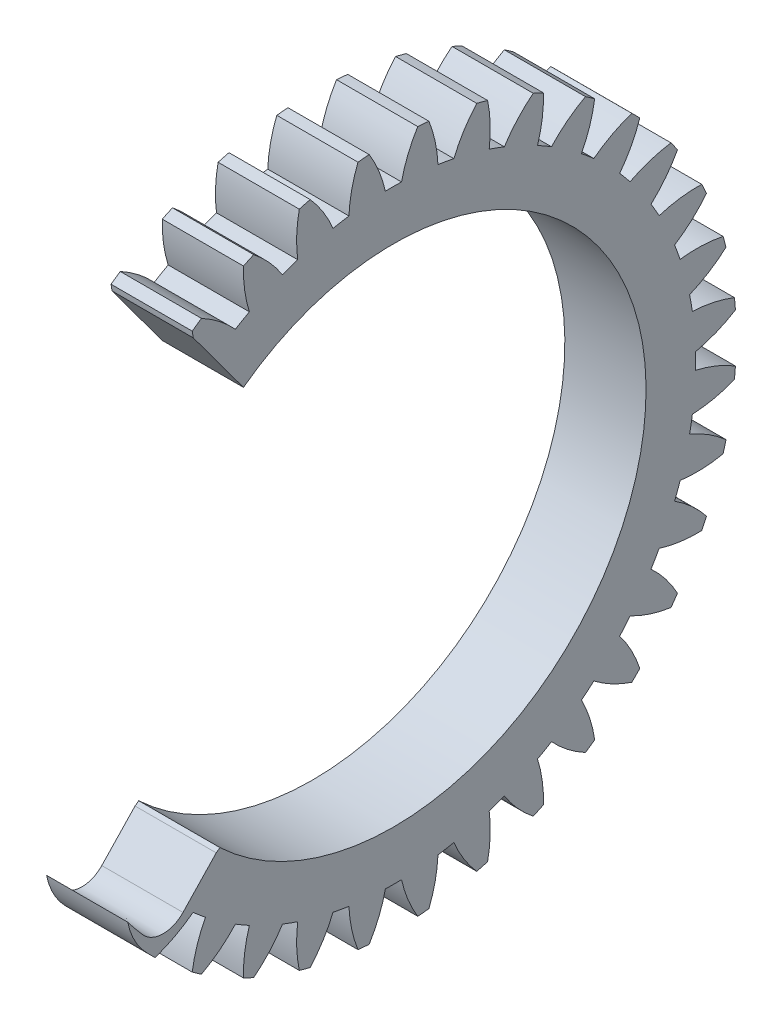
SolidWorks part; units mm, degrees
ref_plane "Plane1" through (0, 0, 0) normal (0, 0, 1) x (1, 0, 0)
ref_plane "Plane2" through (0, 0, 0) normal (0, 1, 0) x (1, 0, 0)
ref_plane "Plane3" through (0, 0, 0) normal (1, 0, 0) x (0, 0, -1)
sketch "HoldingSke" plane through (0, 0, 0) normal (0, 1, 0) x (1, 0, 0)
  line L0 (0, 0) -> (0.4045, -0.2939)
  line L1 (-15, 0) -> (100, 0) construction
  line L2 (0, 0) -> (-2.1039, 2.3779)
  line L3 (0, 0) -> (-11.863, 4.5341)
  line L4 (0, 0) -> (6.9867, 5.0761)
  line L5 (0, 0) -> (-46.8476, -17.4728)
  line L6 (0, 0) -> (-7.4607, -5.0337)
  line L7 (-2.1039, 2.3779) -> (8.6586, 51.2059)
  line L8 (-76.2, 54.61) -> (-71.9, 54.61)
  line L9 (-71.009, 38.7566) -> (-53.1078, 45.2721)
  line L10 (-76.2, 71.12) -> (104.1128, 71.12)
  line L11 (0, 0) -> (-9, 0)
  line L12 (-76.2, 101.6) -> (-76.133, 101.6)
  line L13 (24.9733, 27.94) -> (52.9518, 28.4284)
  line L14 (24.9733, 27.94) -> (24.9743, 27.94)
  line L15 (24.9733, 27.94) -> (100.4006, 29.5858)
  line L16 (-63.627, -2) -> (-12.827, -2)
  circle A0 centre (0, 0) radius 28
  circle A1 centre (0, 0) radius 33.499
  circle A2 centre (0, 0) radius 37.5
  circle A3 centre (0, 0) radius 28
  dimension "Num_teeth" = 36
  dimension "Pitch_radius" = 180.3128
  dimension "Width" = 9
  dimension "Thickness" = 9
sketch "BasProSke" plane through (0, 0, 0) normal (0, 1, 0) x (1, 0, 0)
  line L0 (-10, 0) -> (60, 0) construction
  line L1 (0, 0) -> (0, 38)
  line L2 (0, 0) -> (9, 0)
  line L3 (9, 0) -> (9, 38)
  line L4 (9, 38) -> (0, 38)
  dimension "Thickness" = 9
  dimension "Diameter" = 76
revolve "Base-Revolve" add sketch "BasProSke" angle 360 about L0
sketch "TooCutSke" plane through (0, 0, 0) normal (1, 0, 0) x (0, 0, -1)
  line L1 (0, 0) -> (0, 107) construction
  line L2 (0, 0) -> (-1.6875, 35.9604) construction
  line L3 (0, 0) -> (-6.2701, 71.6676) construction
  line L4 (-1.6875, 35.9604) -> (-3.135, 35.8338) construction
  arc A0 (0.8949, 33.487) -> (-0.8949, 33.487) centre (0, 0) ccw
  arc A1 (2.7061, 37.929) -> (-2.7061, 37.929) centre (0, 0) ccw
  circle A2 centre (0, 0) radius 36 construction
  circle A3 centre (0, 0) radius 33.8289 construction
  arc A4 (-0.8949, 33.487) -> (-2.7061, 37.929) centre (-14.9484, 30.347) ccw
  arc A5 (2.7061, 37.929) -> (0.8949, 33.487) centre (14.9484, 30.347) ccw
extrude "ToothCut" cut sketch "TooCutSke" along normal through all
fillet "Breaks" [suppressed] radius 0.04 tangent propagation no
fillet "RootFillets" [suppressed] radius 0.501
pattern_circular "TeethCuts" count 36 every 10 about axis through (-10, 0, 0) along (1, 0, 0) of "ToothCut", "RootFillets", "Breaks"
sketch "HubNeaOneSke" plane through (0, 0, 0) normal (-1, 0, 0) x (0, 0, 1)
  circle A0 centre (0, 0) radius 33.499
  dimension "Diameter" = 66.998
extrude "HubNearOne" [suppressed] add sketch "HubNeaOneSke" along normal blind 41.0001
sketch "HubNeaBotSke" plane through (0, 0, 0) normal (-1, 0, 0) x (0, 0, 1)
  circle A0 centre (0, 0) radius 33.499
  dimension "Diameter" = 66.998
extrude "HubNearBoth" [suppressed] add sketch "HubNeaBotSke" along normal blind 20.5
ref_plane "FarPln" through (9, 0, 0) normal (1, 0, 0) x (0, 0, -1)
sketch "HubFarSke" plane through (9, 0, 0) normal (1, 0, 0) x (0, 0, -1)
  circle A0 centre (0, 0) radius 33.499
  dimension "Diameter" = 66.998
extrude "HubFar" [suppressed] add sketch "HubFarSke" along normal blind 20.5
sketch "BorSke" plane through (0, 0, 0) normal (1, 0, 0) x (0, 0, -1)
  circle A0 centre (0, 0) radius 28
  dimension "Diameter" = 56
extrude "Bore" cut sketch "BorSke" along normal mid plane 100.0001
sketch "KeySke" plane through (0, 0, 0) normal (1, 0, 0) x (0, 0, -1)
  line L0 (-8, 0) -> (-8, 32.3)
  line L1 (-8, 32.3) -> (8, 32.3)
  line L2 (8, 32.3) -> (8, 0)
  line L3 (0, 0) -> (0, 34) construction
  line L4 (-8, 0) -> (8, 0)
  dimension "Width" = 16
extrude "Keyway" [suppressed] cut sketch "KeySke" along normal mid plane 100.0001
pattern_circular "Keyway2" [suppressed] count 2 every 90 about axis through (-10, 0, 0) along (1, 0, 0) reverse direction yes
sketch "Szkic1" plane through (0, 0, 0) normal (1, 0, 0) x (0, 0, -1)
  line L0 (0, 0) -> (-27.328, 37.0259)
  line L1 (-27.328, 37.0259) -> (-47.6164, -10.233)
  line L2 (-47.6164, -10.233) -> (0, 0)
  point P3 (0, 0)
  point P5 (-27.328, 37.0259)
extrude "Wytnij-wyciągnięcie1" cut sketch "Szkic1" along normal through all
sketch "Szkic2" plane through (0, 0, 0) normal (1, 0, 0) x (0, 0, -1)
  line L0 (-19.6433, -20.6493) -> (-23.3286, -24.5233) construction
  line L1 (-19.6433, -20.6493) -> (-23.3286, -24.5233)
  line L2 (-24.5118, 27.7159) -> (-14.2182, -16.6493)
  line L3 (-14.2182, -16.6493) -> (-19.6433, -20.6493)
  line L4 (-24.5118, 27.7159) -> (-50.9594, 25.255)
  line L5 (-50.9594, 25.255) -> (-37.7356, -29.3697)
  line L6 (-37.7356, -29.3697) -> (-27.7664, -24.4546)
  line L7 (-26.426, -27.3069) -> (-27.3069, -26.426)
  line L8 (-26.426, -27.3069) -> (-25.0675, -25.4318)
  arc A0 (-24.5118, 27.7159) -> (-27.7664, -24.4546) centre (0, 0) ccw construction
  arc A1 (-24.5118, 27.7159) -> (-27.7664, -24.4546) centre (0, 0) ccw
  arc A2 (-27.3069, -26.426) -> (-29.4473, -22.4022) centre (-21.7924, -20.9115) cw
  spline S0 degree 3 poles (1175.5894, 1572.5328) (101.2454, 207.1812) (-45.7493, -11.1584) (-27.1426, -24.9996) (-26.9606, -25.1074) (-26.5829, -25.2806) (-26.3868, -25.3469) (-25.9801, -25.4387) (-25.7711, -25.4633) (-25.3572, -25.469) (-25.1483, -25.4503) (-24.7384, -25.37) (-24.5404, -25.3094) (-24.158, -25.1482) (-23.9725, -25.0463) (-3.8008, -11.0935) (-159.5107, 232.385) (-1180.2525, 1606.4092) knots -13.745703 -13.745703 -13.745703 -13.745703 0.125 0.125 0.25 0.25 0.375 0.375 0.5 0.5 0.625 0.625 0.75 0.75 0.875 0.875 15.522147 15.522147 15.522147 15.522147 only from (-27.7664, -24.4546) to (-23.3286, -24.5233) construction
  spline S1 degree 3 poles (-27.7664, -24.4546) (-27.6277, -24.6121) (-27.4749, -24.7523) (-27.1426, -24.9996) (-26.9606, -25.1074) (-26.5829, -25.2806) (-26.3868, -25.3469) (-25.9801, -25.4387) (-25.7711, -25.4633) (-25.3572, -25.469) (-25.1483, -25.4503) (-24.7384, -25.37) (-24.5404, -25.3094) (-24.158, -25.1482) (-23.9725, -25.0463) (-23.6312, -24.8102) (-23.4733, -24.6754) (-23.3286, -24.5233) knots 0 0 0 0 0.125 0.125 0.25 0.25 0.375 0.375 0.5 0.5 0.625 0.625 0.75 0.75 0.875 0.875 1 1 1 1
extrude "Wytnij-wyciągnięcie2" cut sketch "Szkic2" against normal blind 43 and the other way through all contours A1 L4 L5 L6 | A1 S1 L1 L3 L2 region at (0, -1.5762, 26.5296) region at (0, 4.8425, 39.1923)
extrude "Dodanie-wyciągnięcie1" add sketch "Szkic2<3>" along normal up to surface (9 mm away) contours A2 L6 A1 | S1 L6 A2 L7 L8 region at (0, -25.7946, 26.8655) region at (0, -23.8723, 28.649) up to face at (9, -1.2954, -9.9994)
sketch "Szkic2<3>" plane through (0, 0, 0) normal (1, 0, 0) x (0, 0, -1) same geometry as "Szkic2"
equation "' \"Module@HoldingSke\" = 6.35"
equation "' \"Num_teeth@HoldingSke\" = 12"
equation "' \"Ap@HoldingSke\" =  20"
equation "' \"Ap@HoldingSke\" = 20"
equation "' \"Width@HoldingSke\" = 0.5 * 25.4"
equation "' \"Hub_dia@HoldingSke\"= 1 * 25.4"
equation "' \"Hub_dia@HoldingSke\" = 1 * 25.4"
equation "' \"Overall_len@HoldingSke\" = 1.0 * 25.4"
equation "' \"Bore@HoldingSke\" = 0.75 * 25.4"
equation "' \"T_dim@HoldingSke\" = 0.1 * 25.4"
equation "' \"Width@KeySke\" = 0.25 * 25.4"
equation "' \"Show_teeth@HoldingSke\" = 13"
equation "' \"Backlash@HoldingSke\" = 0.009 * 25.4"
equation "' \"Addendum_fac@HoldingSke\" = 1.0"
equation "' \"Dedendum_fac@HoldingSke\" = 1.25"
equation "' \"Dedendum_add@HoldingSke\" = 0.00005 * 25.4"
equation "' \"Clearance_fac@HoldingSke\" = 0.25"
equation "\"Pitch@HoldingSke\" = 1 / \"Module@HoldingSke\""
equation "\"Overcut_dia@TooCutSke\" = (\"Num_teeth@HoldingSke\" + 2 * \"Addendum_fac@HoldingSke\") / \"Pitch@HoldingSke\" + 0.002 * 25.4"
equation "\"Pitch_dia@TooCutSke\" = \"Num_teeth@HoldingSke\" / \"Pitch@HoldingSke\""
equation "\"Base_dia@TooCutSke\" = \"Num_teeth@HoldingSke\" / \"Pitch@HoldingSke\" * cos((\"Ap@HoldingSke\"  * 3.14159265 / 180))"
equation "\"Root_dia@TooCutSke\" = (\"Num_teeth@HoldingSke\" + 2) / \"Pitch@HoldingSke\" - 2 * (\"Addendum_fac@HoldingSke\" + \"Dedendum_fac@HoldingSke\") / \"Pitch@HoldingSke\" - \"Dedendum_add@HoldingSke\" * 2"
equation "\"Half_ang@TooCutSke\" = 180 / \"Num_teeth@HoldingSke\""
equation "\"Half_CT@TooCutSke\" = \"Num_teeth@HoldingSke\" / \"Pitch@HoldingSke\" * sin((3.14159265 / 2 / \"Num_teeth@HoldingSke\")) / 2 - 7 * \"Backlash@HoldingSke\" / 4"
equation "\"Flank_rad@TooCutSke\" = \"Num_teeth@HoldingSke\" / \"Pitch@HoldingSke\" / 5"
equation "\"Radius@RootFillets\" = \"Clearance_fac@HoldingSke\" / \"Pitch@HoldingSke\" + \"Dedendum_add@HoldingSke\""
equation "\"Break_rad@Breaks\" = 0.02 / \"Pitch@HoldingSke\""
equation "\"Thickness@HoldingSke\" = \"Width@HoldingSke\""
equation "\"OAL@HoldingSke\" = \"Thickness@HoldingSke\""
equation "\"MHD@HoldingSke\" = (\"Num_teeth@HoldingSke\" + 2) / \"Pitch@HoldingSke\" - 2 * (\"Addendum_fac@HoldingSke\" + \"Dedendum_fac@HoldingSke\")  / \"Pitch@HoldingSke\" - \"Dedendum_add@HoldingSke\" * 2"
equation "\"MBD@HoldingSke\" = (\"Num_teeth@HoldingSke\" + 2) / \"Pitch@HoldingSke\" - 2 * (\"Addendum_fac@HoldingSke\" + \"Dedendum_fac@HoldingSke\")  / \"Pitch@HoldingSke\" - \"Dedendum_add@HoldingSke\" * 2 - 0.002 * 25.4"
equation "\"MHD@HoldingSke\" = ((sgn( \"MHD@HoldingSke\" - \"Hub_dia@HoldingSke\" )-1)*( \"MHD@HoldingSke\" - \"Hub_dia@HoldingSke\" ))/-2+ \"Hub_dia@HoldingSke\""
equation "\"MBD@HoldingSke\" = ((sgn( \"MBD@HoldingSke\" - \"Bore@HoldingSke\" )-1)*( \"MBD@HoldingSke\" - \"Bore@HoldingSke\" ))/-2+ \"Bore@HoldingSke\""
equation "\"OAL@HoldingSke\" = ((sgn( \"OAL@HoldingSke\" - \"Overall_len@HoldingSke\" )+1)*( \"OAL@HoldingSke\" - \"Overall_len@HoldingSke\" ))/2 + \"Overall_len@HoldingSke\" + 0.000002 * 25.4"
equation "\"Num_teeth@TeethCuts\" = int( \"Show_teeth@HoldingSke\" ) + 1"
equation "\"Num_teeth@TeethCuts\" = ((sgn( \"Num_teeth@TeethCuts\" - \"Num_teeth@HoldingSke\" )-1)*( \"Num_teeth@TeethCuts\" - \"Num_teeth@HoldingSke\" ))/-2+ \"Num_teeth@HoldingSke\""
equation "\"Num_teeth@TeethCuts\" = ((sgn( \"Num_teeth@TeethCuts\" - 2.0)+1)*( \"Num_teeth@TeethCuts\" - 2.0))/2 +2.0"
equation "\"Angle@TeethCuts\" = 360.0 / \"Num_teeth@HoldingSke\""
equation "\"Diameter@BasProSke\" = (\"Num_teeth@HoldingSke\" + 2 * \"Addendum_fac@HoldingSke\") / \"Pitch@HoldingSke\""
equation "\"Thickness@BasProSke\"  = \"Thickness@HoldingSke\""
equation "' \"Fillet_rad@BasProSke\" =  \"Thickness@HoldingSke\" * 0.05"
equation "' \"Fillet_rad@BasProSke\" = \"Thickness@HoldingSke\" * 0.05"
equation "\"MHD@HoldingSke\" = ((sgn( \"MHD@HoldingSke\" - \"Root_dia@TooCutSke\" )-1)*( \"MHD@HoldingSke\" - \"Root_dia@TooCutSke\" ))/-2+ \"Root_dia@TooCutSke\""
equation "\"Diameter@HubNeaOneSke\" = \"MHD@HoldingSke\""
equation "\"Length@HubNearOne\" = \"OAL@HoldingSke\" - \"Thickness@BasProSke\""
equation "\"Diameter@HubNeaBotSke\" = \"MHD@HoldingSke\""
equation "\"Length@HubNearBoth\" = ( \"OAL@HoldingSke\" - \"Thickness@BasProSke\" ) / 2.0"
equation "\"Thickness@FarPln\" = \"Thickness@BasProSke\""
equation "\"Diameter@HubFarSke\" = \"MHD@HoldingSke\""
equation "\"Length@HubFar\" = ( \"OAL@HoldingSke\" - \"Thickness@BasProSke\" ) / 2.0"
equation "\"Diameter@BorSke\" = \"MBD@HoldingSke\""
equation "\"D1@Bore\" = \"OAL@HoldingSke\" * 2.0"
equation "\"D1@Keyway\" = \"OAL@HoldingSke\" * 2.0"
equation "\"Offset@KeySke\" = \"T_dim@HoldingSke\" + \"MBD@HoldingSke\" / 2.0"
